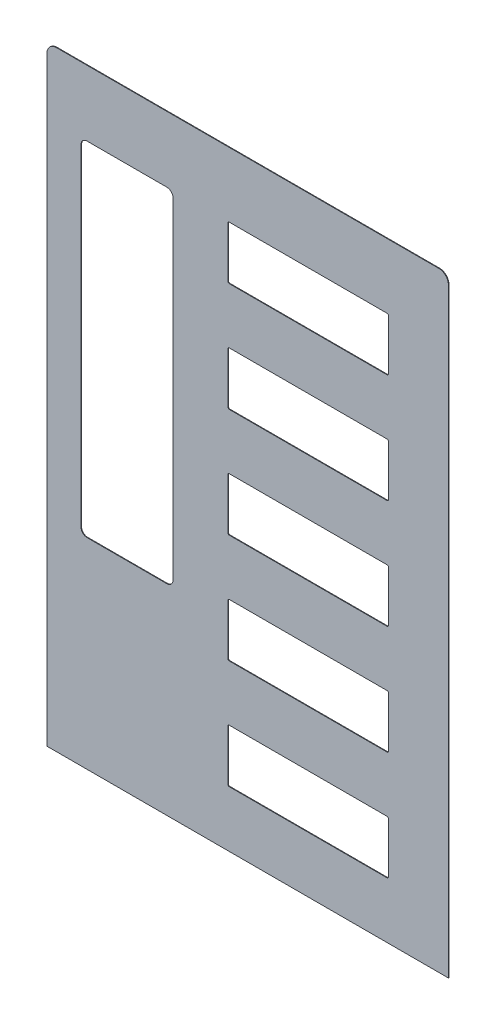
SolidWorks part; units mm, degrees
ref_plane "Front Plane" through (0, 0, 0) normal (0, 0, 1) x (1, 0, 0)
ref_plane "Top Plane" through (0, 0, 0) normal (0, 1, 0) x (1, 0, 0)
ref_plane "Right Plane" through (0, 0, 0) normal (1, 0, 0) x (0, 0, -1)
sketch "Sketch1" plane through (0, 0, 0) normal (0, 0, 1) x (1, 0, 0)
  line L1 (0, 0) -> (663.4, 0)
  line L2 (0, 0) -> (0, 992)
  line L3 (15.7, 1007.7) -> (647.7, 1007.7)
  line L4 (663.4, 0) -> (663.4, 992)
  arc A0 (647.7, 1007.7) -> (663.4, 992) centre (647.7, 992) cw
  arc A1 (0, 992) -> (15.7, 1007.7) centre (15.7, 992) cw
  dimension "D3" = 15.7
  dimension "D1" = 663.4
  dimension "D2" = 1007.7
base flange "Base-Flange1" sketch "Sketch1" thickness 1 reverse thickness direction no parameters "D1"=1
edge flange "Edge-Flange1" [suppressed] sketch "Sketch8" flange angle 90 flange position material inside bend radius 1 thickness 1
sketch "Sketch8" plane through (0, 0, -1) normal (0, -1, 0) x (-1, 0, 0)
  line L0 (0, 0) -> (-822, 0) construction
  line L1 (-42, 0) -> (-780, 0)
  line L2 (-780, 0) -> (-780, 12)
  line L3 (-780, 12) -> (-42, 12)
  line L4 (-42, 12) -> (-42, 0)
  line L5 (0, 0) -> (0, -1) construction
  line L6 (-822, 0) -> (-822, -1) construction
  circle A0 centre (-81, 6) radius 2.75
  circle A1 centre (-261, 6) radius 2.75
  circle A2 centre (-441, 6) radius 2.75
  circle A3 centre (-621, 6) radius 2.75
  circle A4 centre (-801, 6) radius 2.75
  circle A5 centre (-981, 6) radius 2.75
  circle A6 centre (-1161, 6) radius 2.75
  point P6 (-42, 6)
  dimension "D1" = 5.5
  dimension "D2" = 39
  dimension "D4" = 42
  dimension "D5" = 42
  dimension "D3" = 7
bend "EdgeBend1" bend radius 1 bend angle 90 parameters "D5"=1, "D6"=10, "D7"=12
sketch "Sketch9" plane through (0, 0, 0) normal (0, 0, 1) x (1, 0, 0)
  line L0 (663.4, 0) -> (663.4, 992) construction
  line L1 (562.2, 900.7) -> (301.2, 900.7)
  line L2 (564.2, 898.7) -> (564.2, 814.7)
  line L3 (562.2, 812.7) -> (301.2, 812.7)
  line L4 (299.2, 898.7) -> (299.2, 814.7)
  line L5 (647.7, 1007.7) -> (15.7, 1007.7) construction
  line L38 (564.2, 718.7) -> (564.2, 634.7)
  line L39 (562.2, 720.7) -> (301.2, 720.7)
  line L40 (562.2, 632.7) -> (301.2, 632.7)
  line L41 (299.2, 718.7) -> (299.2, 634.7)
  line L42 (564.2, 538.7) -> (564.2, 454.7)
  line L43 (562.2, 540.7) -> (301.2, 540.7)
  line L44 (562.2, 452.7) -> (301.2, 452.7)
  line L45 (299.2, 538.7) -> (299.2, 454.7)
  line L46 (564.2, 358.7) -> (564.2, 274.7)
  line L47 (562.2, 360.7) -> (301.2, 360.7)
  line L48 (562.2, 272.7) -> (301.2, 272.7)
  line L49 (299.2, 358.7) -> (299.2, 274.7)
  line L74 (564.2, 178.7) -> (564.2, 94.7)
  line L75 (562.2, 180.7) -> (301.2, 180.7)
  line L76 (562.2, 92.7) -> (301.2, 92.7)
  line L77 (299.2, 178.7) -> (299.2, 94.7)
  arc A0 (564.2, 814.7) -> (562.2, 812.7) centre (562.2, 814.7) cw
  arc A1 (301.2, 812.7) -> (299.2, 814.7) centre (301.2, 814.7) cw
  arc A2 (301.2, 900.7) -> (299.2, 898.7) centre (301.2, 898.7) ccw
  arc A3 (562.2, 900.7) -> (564.2, 898.7) centre (562.2, 898.7) cw
  arc A36 (562.2, 720.7) -> (564.2, 718.7) centre (562.2, 718.7) cw
  arc A37 (564.2, 634.7) -> (562.2, 632.7) centre (562.2, 634.7) cw
  arc A38 (301.2, 632.7) -> (299.2, 634.7) centre (301.2, 634.7) cw
  arc A39 (301.2, 720.7) -> (299.2, 718.7) centre (301.2, 718.7) ccw
  arc A40 (562.2, 540.7) -> (564.2, 538.7) centre (562.2, 538.7) cw
  arc A41 (564.2, 454.7) -> (562.2, 452.7) centre (562.2, 454.7) cw
  arc A42 (301.2, 452.7) -> (299.2, 454.7) centre (301.2, 454.7) cw
  arc A43 (301.2, 540.7) -> (299.2, 538.7) centre (301.2, 538.7) ccw
  arc A44 (562.2, 360.7) -> (564.2, 358.7) centre (562.2, 358.7) cw
  arc A45 (564.2, 274.7) -> (562.2, 272.7) centre (562.2, 274.7) cw
  arc A46 (301.2, 272.7) -> (299.2, 274.7) centre (301.2, 274.7) cw
  arc A47 (301.2, 360.7) -> (299.2, 358.7) centre (301.2, 358.7) ccw
  arc A72 (562.2, 180.7) -> (564.2, 178.7) centre (562.2, 178.7) cw
  arc A73 (564.2, 94.7) -> (562.2, 92.7) centre (562.2, 94.7) cw
  arc A74 (301.2, 92.7) -> (299.2, 94.7) centre (301.2, 94.7) cw
  arc A75 (301.2, 180.7) -> (299.2, 178.7) centre (301.2, 178.7) ccw
  dimension "D5" = 2
  dimension "D1" = 99.2
  dimension "D2" = 265
  dimension "D3" = 88
  dimension "D4" = 107
  dimension "D6" = 1
  dimension "D7" = 5
extrude "Cut-Extrude1" cut sketch "Sketch9" against normal blind 10 normal cut yes
sketch "Sketch10" plane through (0, 0, 0) normal (0, 0, 1) x (1, 0, 0)
  line L1 (66.2, 331.7) -> (198.2, 331.7)
  line L2 (56.2, 341.7) -> (56.2, 889.2)
  line L3 (66.2, 899.2) -> (198.2, 899.2)
  line L4 (208.2, 341.7) -> (208.2, 889.2)
  line L6 (663.4, 0) -> (663.4, 992) construction
  line L8 (647.7, 1007.7) -> (15.7, 1007.7) construction
  arc A0 (66.2, 331.7) -> (56.2, 341.7) centre (66.2, 341.7) cw
  arc A1 (198.2, 331.7) -> (208.2, 341.7) centre (198.2, 341.7) ccw
  arc A2 (56.2, 889.2) -> (66.2, 899.2) centre (66.2, 889.2) cw
  arc A3 (198.2, 899.2) -> (208.2, 889.2) centre (198.2, 889.2) cw
  dimension "D5" = 10
  dimension "D1" = 152
  dimension "D2" = 567.5
  dimension "D3" = 108.5
  dimension "D4" = 455.2
extrude "Cut-Extrude2" cut sketch "Sketch10" against normal blind 10 normal cut yes
sketch "Bend-Lines1" [suppressed] plane through (0, 0, 0) normal (0, 1, 0) x (1, 0, 0)
sketch "Bounding-Box1" [suppressed] plane through (0, 0, 0) normal (0, 1, 0) x (1, 0, 0)
sheet metal parameters "Sheet-Metal1" thickness 1 parameters "D1"=2
flat pattern "Flat-Pattern1" [suppressed]
sketch "Bend-Lines2" plane through (0, 0, 0) normal (0, 1, 0) x (1, 0, 0)
sketch3d "Bounding-Box2" [suppressed]
  line L0 (15, 15, 0) -> (-1227, 15, 0) construction
  line L1 (15, -935, 0) -> (-1227, -935, 0) construction
  line L2 (15, 15, 0) -> (15, -935, 0) construction
  line L3 (-1227, 15, 0) -> (-1227, -935, 0) construction
sheet metal parameters "Sheet-Metal2" thickness 1 parameters "D1"=2
flat pattern "Flat-Pattern1"
sketch "Bend-Lines2" plane through (0, 0, 0) normal (0, 0, 1) x (1, 0, 0)
  line L0 (0, 0.8219) -> (1242, 0.8219) construction
  line L1 (0, 0.8219) -> (1242, 0.8219) construction
sketch3d "Bounding-Box2" [suppressed]
  line L0 (-15, 15, 0) -> (1227, 15, 0) construction
  line L1 (-15, -946.3562, 0) -> (1227, -946.3562, 0) construction
  line L2 (-15, 15, 0) -> (-15, -946.3562, 0) construction
  line L3 (1227, 15, 0) -> (1227, -946.3562, 0) construction
bend of the flat pattern "Flatten-<EdgeBend1>1"
sheet metal parameters "Sheet-Metal3" thickness 1 parameters "D1"=2
flat pattern "Flat-Pattern1"
sketch "Bend-Lines2" plane through (0, 0, 0) normal (0, 0, 1) x (1, 0, 0)
  line L0 (0, 0.8219) -> (1244, 0.8219) construction
  line L1 (0, 0.8219) -> (1244, 0.8219) construction
sketch3d "Bounding-Box2" [suppressed]
  line L0 (-16, 16, 0) -> (1228, 16, 0) construction
  line L1 (-16, -945.3562, 0) -> (1228, -945.3562, 0) construction
  line L2 (-16, 16, 0) -> (-16, -945.3562, 0) construction
  line L3 (1228, 16, 0) -> (1228, -945.3562, 0) construction
sheet metal parameters "Sheet-Metal4" thickness 1 parameters "D1"=2
flat pattern "Flat-Pattern1"
sketch "Bend-Lines2" plane through (0, 0, 0) normal (0, 0, 1) x (1, 0, 0)
sketch3d "Bounding-Box2" [suppressed]
  line L0 (647.7, -992, 0) -> (647.7, 15.7, 0) construction
  line L1 (-15.7, -992, 0) -> (-15.7, 15.7, 0) construction
  line L2 (647.7, -992, 0) -> (-15.7, -992, 0) construction
  line L3 (647.7, 15.7, 0) -> (-15.7, 15.7, 0) construction
equation "\"D5@Sketch8\"=\"D4@Sketch8\""
